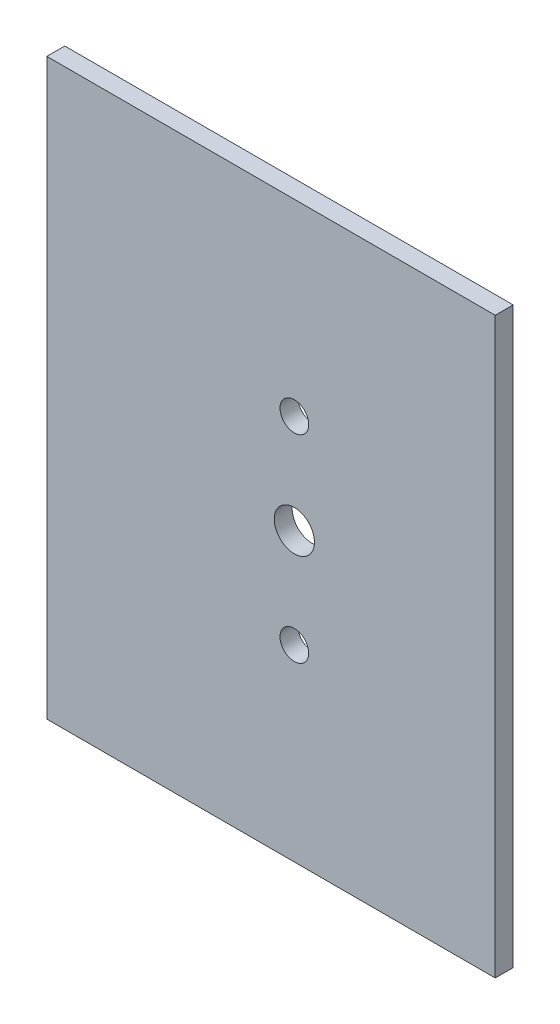
SolidWorks part; units mm, degrees
material "6061-T6 (SS)"
ref_plane "X-Y Datum" through (0, 0, 0) normal (0, 0, 1) x (1, 0, 0)
ref_plane "X-Z Datum" through (0, 0, 0) normal (0, 1, 0) x (1, 0, 0)
ref_plane "Y-Z Datum" through (0, 0, 0) normal (1, 0, 0) x (0, 0, -1)
sketch "Sketch2" plane through (0, 0, 0) normal (1, 0, 0) x (0, 0, -1)
  line L1 (11.43, -25.4) -> (-11.43, -25.4)
  line L2 (11.43, -25.4) -> (11.43, 25.4)
  line L3 (11.43, 25.4) -> (-11.43, 25.4)
  line L4 (-11.43, -25.4) -> (-11.43, 25.4)
  line L5 (11.43, -25.4) -> (-11.43, 25.4) construction
  line L6 (11.43, 25.4) -> (-11.43, -25.4) construction
  point P0 (0, 0)
  dimension "D1" = 50.8
  dimension "D2" = 22.86
extrude "Boss-Extrude1" add sketch "Sketch2" along normal blind 1.5875
sketch "Sketch3" plane through (1.5875, 0, 0) normal (1, 0, 0) x (0, 0, -1)
  line L0 (11.43, 25.4) -> (-11.43, 25.4) construction
  line L1 (-11.43, -25.4) -> (-9.8425, -25.4)
  line L2 (-11.43, -25.4) -> (-11.43, 25.4)
  line L3 (-11.43, 25.4) -> (-9.8425, 25.4)
  line L4 (-9.8425, -25.4) -> (-9.8425, 25.4)
  dimension "D1" = 1.5875
extrude "Boss-Extrude2" add sketch "Sketch3" along normal blind 38.1
sketch "Sketch4" plane through (0, 0, 11.43) normal (0, 0, 1) x (1, 0, 0)
  line L0 (39.6875, 25.4) -> (39.6875, -25.4) construction
  line L1 (55, 0) -> (-55, 0) construction
  circle A0 centre (21.9075, 0) radius 1.778
  circle A1 centre (21.9075, 8.763) radius 1.27
  circle A2 centre (21.9075, -8.763) radius 1.27
  dimension "D1" = 2.54
  dimension "D2" = 3.556
  dimension "D3" = 8.763
  dimension "D4" = 17.78
  dimension "D5" = 8.763
extrude "Cut-Extrude1" cut sketch "Sketch4" against normal up to next
split "Split1" bodies to split 103 resulting bodies 105 split by face at (23.1775, -8.763, 9.8425)
